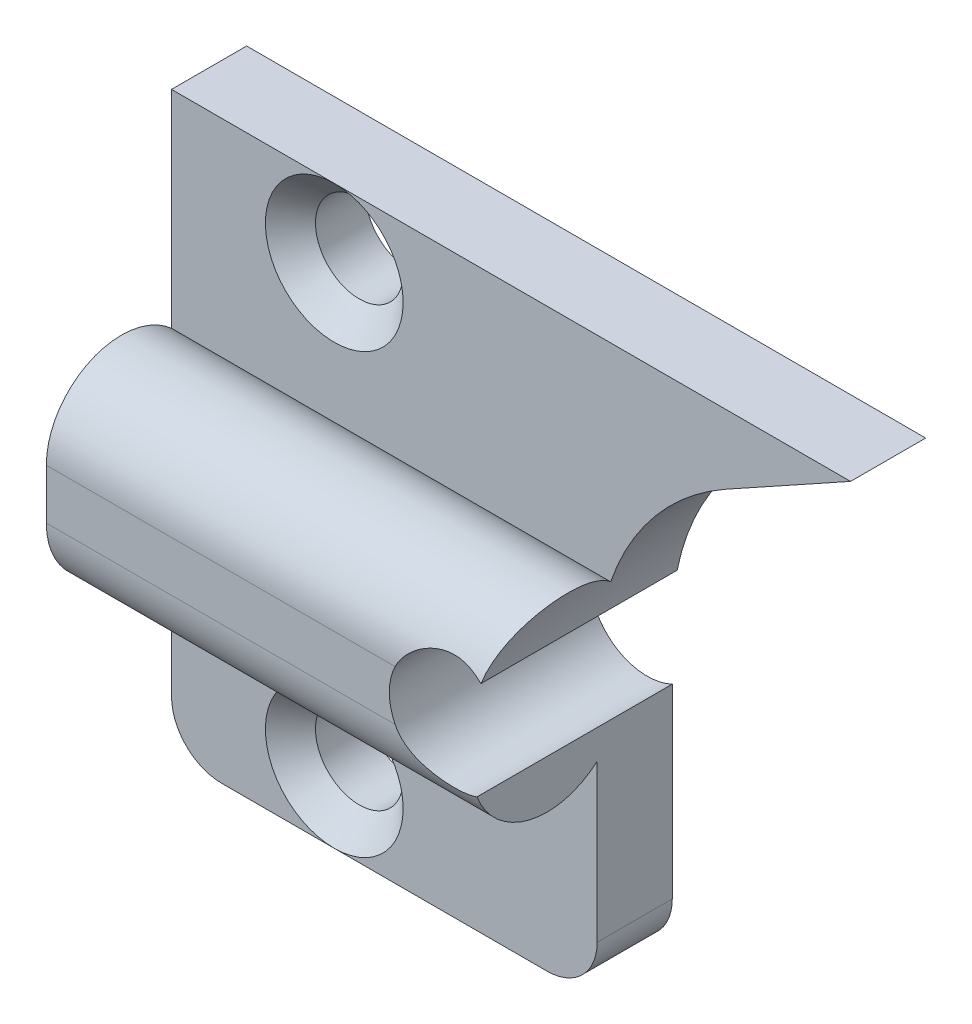
SolidWorks part; units mm, degrees
ref_plane "Alzado" through (0, 0, 0) normal (0, 0, 1) x (1, 0, 0)
ref_plane "Planta" through (0, 0, 0) normal (0, 1, 0) x (1, 0, 0)
ref_plane "Vista lateral" through (0, 0, 0) normal (1, 0, 0) x (0, 0, -1)
sketch "Guia" plane through (0, 0, 0) normal (0, 0, 1) x (1, 0, 0)
  line L0 (0, 0) -> (49, 0)
  line L1 (49, 0) -> (32.8558, 29.1248)
  dimension "D1" = 49
  dimension "D2" = 33.3
  dimension "D3" = 61
ref_plane "Plano1" through (0, 0, -3) normal (0, 0, 1) x (1, 0, 0)
sketch "Croquis3" plane through (0, 0, -3) normal (0, 0, 1) x (1, 0, 0)
  line L0 (9.5, 8.75) -> (9.5, -8.75) construction
  line L1 (3, 11.5) -> (41, 11.5)
  line L2 (3, 11.5) -> (3, -11.5)
  line L3 (3, -11.5) -> (41, -11.5)
  line L4 (41, 11.5) -> (41, -11.5)
  circle A0 centre (9.5, 8.75) radius 1.75
  circle A1 centre (9.5, -8.75) radius 1.75
  arc A2 (20.1847, -1.9129) -> (20.1847, 1.9129) centre (30, 0) ccw
  arc A3 (20.1847, 1.9129) -> (20.1847, -1.9129) centre (19, 0) ccw
  point P4 (3, 0)
  point P8 (9.5, 0)
  dimension "D5" = 3.5
  dimension "D6" = 3.5
  dimension "D7" = 11
  dimension "D8" = 20
  dimension "D10" = 4.5
  dimension "D1" = 38
  dimension "D2" = 23
  dimension "D3" = 31.5
  dimension "D4" = 17.5
  dimension "D9" = 22
  dimension "D11" = 3
extrude "Saliente-Extruir1" add sketch "Croquis3" along normal blind 1
sketch "Croquis4" plane through (3, 0, 0) normal (1, 0, 0) x (0, 0, -1)
  line L0 (0, 1) -> (0, -1) construction
  line L1 (3, 1) -> (3, -1)
  line L2 (-3, 1) -> (-3, -1)
  arc A0 (3, 1) -> (-3, 1) centre (0, 1) ccw
  arc A1 (-3, -1) -> (3, -1) centre (0, -1) ccw
  point P3 (0, 0)
  dimension "D1" = 6
  dimension "D2" = 2
extrude "Saliente-Extruir2" add sketch "Croquis4" along normal blind 25
ref_plane "Plano3" through (49, 0, 0) normal (-0.4848, 0.8746, 0) x (0.8746, 0.4848, 0)
sketch "Croquis8" plane through (49, 0, 0) normal (-0.4848, 0.8746, 0) x (0.8746, 0.4848, 0)
  line L0 (-1, 0) -> (1, 0) construction
  line L1 (-1, 3) -> (1, 3)
  line L2 (-1, -3) -> (1, -3)
  arc A0 (-1, 3) -> (-1, -3) centre (-1, 0) ccw
  arc A1 (1, -3) -> (1, 3) centre (1, 0) ccw
  point P2 (0, 0)
  dimension "D1" = 6
  dimension "D2" = 2
extrude "Saliente-Extruir4" add sketch "Croquis8" along normal blind 40 separate body
sketch "Croquis9" plane through (0, 0, -3) normal (0, 0, 1) x (1, 0, 0)
  line L4 (25.1519, 8.7462) -> (39.6861, 16.8027)
  line L6 (49, 0) -> (32.8558, 29.1248) construction
  line L7 (39.6861, 16.8027) -> (36.2925, 22.925)
  line L8 (36.2925, 22.925) -> (21.7582, 14.8685)
  line L9 (13, 0) -> (20, 0)
  arc A1 (25.1519, 8.7462) -> (20, 0) centre (30, 0) ccw
  arc A2 (21.7582, 14.8685) -> (13, 0) centre (30, 0) ccw
  dimension "D1" = 10
  dimension "D2" = 7
extrude "Saliente-Extruir5" add sketch "Croquis9" along normal blind 6
sketch "Croquis10" plane through (0, 0, -3) normal (0, 0, -1) x (-1, 0, 0)
  line L0 (-54.7522, 25.1539) -> (-25.1519, 8.7462)
  line L1 (-20, -2.0712) -> (-20, -15.3934)
  line L2 (-20, -15.3934) -> (-54.7522, -15.3934)
  line L3 (-54.7522, -15.3934) -> (-54.7522, 25.1539)
  line L4 (-30.1199, 11.5) -> (-38.8115, 16.3178) construction
  arc A0 (-20, -2.0712) -> (-20.195, 1.9652) centre (-19, 0) ccw
  arc A1 (-20.195, 1.9652) -> (-25.1519, 8.7462) centre (-30, 0) ccw
  dimension "D1" = 4.6
  dimension "D2" = 10
extrude "Cortar-Extruir3" cut sketch "Croquis10" against normal through all
sketch "Croquis5" plane through (3, 0, 0) normal (1, 0, 0) x (0, 0, -1)
  circle A0 centre (0, 0) radius 1.75
  dimension "D1" = 3.5
extrude "Cortar-Extruir1" cut sketch "Croquis5" along normal blind 12
sketch "Croquis11" plane through (-7.8754, 14.2076, 0) normal (-0.4848, 0.8746, 0) x (0.8746, 0.4848, 0)
  line L0 (42.8564, 3) -> (42.8564, -3) construction
  line L1 (43.8564, 3) -> (41.8564, 3) construction
  line L2 (41.8564, -3) -> (43.8564, -3) construction
  circle A0 centre (42.8564, 0) radius 1.75
  dimension "D1" = 3.5
extrude "Cortar-Extruir4" cut sketch "Croquis11" against normal through all
sketch "Croquis12" plane through (0, 0, -3) normal (0, 0, -1) x (-1, 0, 0)
  line L0 (-41.8182, 31.0299) -> (-23.8934, 27.2198)
  line L1 (-49, 0) -> (-32.8558, 29.1248) construction
  line L2 (-41.8182, 31.0299) -> (-26.8491, 44.5194)
  line L3 (-26.8491, 44.5194) -> (-23.8934, 27.2198)
  point P2 (-32.8558, 29.1248)
  dimension "D1" = 73
extrude "Cortar-Extruir5" cut sketch "Croquis12" against normal through all
fillet "Redondeo1" radius 2 3 edges at (3, 11.5, -2.5) (3, -11.5, -2.5) (20, -11.5, -2.5)
sketch "Croquis13" plane through (0, 0, -3) normal (0, 0, -1) x (-1, 0, 0)
  line L9 (-20, -2.0712) -> (-20, -9.5)
  line L10 (-18, -11.5) -> (-5, -11.5)
  line L11 (-3, -9.5) -> (-3, 9.5)
  line L12 (-5, 11.5) -> (-17.48, 11.5)
  line L13 (-21.7582, 14.8685) -> (-35.4178, 22.4402)
  line L14 (-35.4178, 22.4402) -> (-31.833, 28.9074)
  line L15 (-31.833, 28.9074) -> (-33.8787, 29.3422)
  line L16 (-33.8787, 29.3422) -> (-40.5608, 17.2875)
  line L17 (-40.5608, 17.2875) -> (-25.1519, 8.7462)
  line L18 (-20, -2.0712) -> (-20, -9.5)
  line L19 (-18, -11.5) -> (-5, -11.5)
  line L20 (-3, -9.5) -> (-3, 9.5)
  line L21 (-5, 11.5) -> (-17.48, 11.5)
  line L22 (-21.7582, 14.8685) -> (-35.4178, 22.4402)
  line L23 (-35.4178, 22.4402) -> (-31.833, 28.9074)
  line L24 (-31.833, 28.9074) -> (-33.8787, 29.3422)
  line L25 (-33.8787, 29.3422) -> (-40.5608, 17.2875)
  line L26 (-40.5608, 17.2875) -> (-25.1519, 8.7462)
  circle A3 centre (-9.5, -8.75) radius 1.75 construction
  circle A4 centre (-9.5, 8.75) radius 1.75 construction
  circle A5 centre (-9.5, -8.75) radius 1.75
  circle A6 centre (-9.5, 8.75) radius 1.75
  arc A9 (-20, -9.5) -> (-18, -11.5) centre (-18, -9.5) ccw
  arc A10 (-5, -11.5) -> (-3, -9.5) centre (-5, -9.5) ccw
  arc A11 (-3, 9.5) -> (-5, 11.5) centre (-5, 9.5) ccw
  arc A12 (-17.48, 11.5) -> (-21.7582, 14.8685) centre (-30, 0) ccw
  arc A13 (-20.195, 1.9652) -> (-25.1519, 8.7462) centre (-30, 0) ccw
  arc A14 (-20, -2.0712) -> (-20.195, 1.9652) centre (-19, 0) ccw
  arc A15 (-20, -9.5) -> (-18, -11.5) centre (-18, -9.5) ccw
  arc A16 (-5, -11.5) -> (-3, -9.5) centre (-5, -9.5) ccw
  arc A17 (-3, 9.5) -> (-5, 11.5) centre (-5, 9.5) ccw
  arc A18 (-17.48, 11.5) -> (-21.7582, 14.8685) centre (-30, 0) ccw
  arc A19 (-20.195, 1.9652) -> (-25.1519, 8.7462) centre (-30, 0) ccw
  arc A20 (-20, -2.0712) -> (-20.195, 1.9652) centre (-19, 0) ccw
  dimension "D1" = 0
extrude "Saliente-Extruir6" add sketch "Croquis13" along normal blind 2
chamfer "Chaflán1" distance 1 angle 45 2 edges at (11.25, -8.75, -2) (11.25, 8.75, -2)
extrude "Cortar-Extruir6" cut sketch "Croquis14" against normal through all
sketch "Croquis14" plane through (3, 0.0247, -35.3274) normal (-1, 0, 0) x (0, 0, 1)
  line L1 (-38.6726, 3.2113) -> (-38.6726, 11.4753)
  line L2 (-38.6726, 11.4753) -> (-35.6726, 11.4753)
  line L3 (33.3274, 11.4753) -> (33.3274, 3.2113)
  line L4 (-43.6726, 0.9753) -> (-43.6726, 29.9697)
  line L5 (-43.6726, 29.9697) -> (-35.6726, 29.9697)
  line L6 (38.3274, 29.9697) -> (38.3274, 0.9753)
  line L7 (-35.6726, 11.4753) -> (-35.6726, 29.9697)
  line L8 (30.3274, 11.4753) -> (30.3274, 29.9697)
  line L9 (30.3274, 11.4753) -> (33.3274, 11.4753)
  line L10 (30.3274, 29.9697) -> (38.3274, 29.9697)
  arc A0 (38.3274, 0.9753) -> (33.3274, 3.2113) centre (35.3274, 0.9753) ccw
  arc A2 (-38.6726, 3.2113) -> (-43.6726, 0.9753) centre (-40.6726, 0.9753) ccw
  point P11 (0, 0)
  point P12 (0, 0)
  point P16 (-38.6726, 11.4753)
  point P17 (0, 0)
sketch "Croquis15" plane through (0, 0, -2) normal (0, 0, 1) x (1, 0, 0)
  line L0 (3, 9.5) -> (3, 11.5)
  line L1 (3, 11.5) -> (5, 11.5)
  arc A0 (5, 11.5) -> (3, 9.5) centre (5, 9.5) ccw
extrude "Saliente-Extruir7" add sketch "Croquis15" against normal up to surface (3 mm away) up to face at (14.4911, -0.0564, -5)
